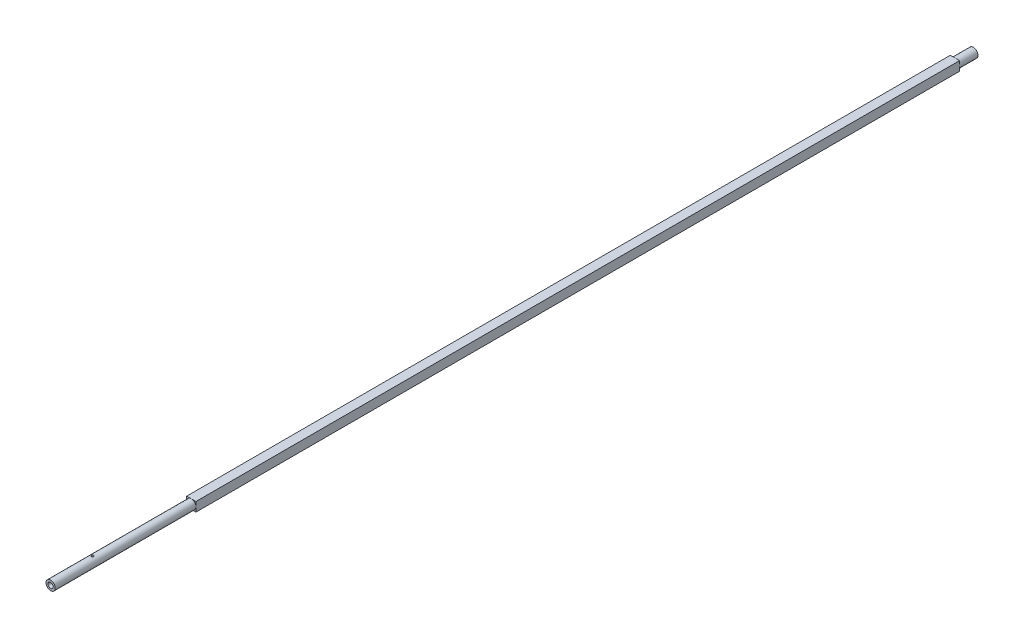
SolidWorks part; units mm, degrees
material "1060 Alloy"
ref_plane "Front Plane" through (0, 0, 0) normal (0, 0, 1) x (1, 0, 0)
ref_plane "Top Plane" through (0, 0, 0) normal (0, 1, 0) x (1, 0, 0)
ref_plane "Right Plane" through (0, 0, 0) normal (1, 0, 0) x (0, 0, -1)
sketch "Sketch1" plane through (0, 0, 0) normal (1, 0, 0) x (0, 0, -1)
  line L0 (0, 0) -> (-3.0596, 0) construction
  line L1 (533.7, 1.805) -> (528.7, 0)
  line L2 (-96.02, 1.805) -> (-96.02, 3.155)
  line L3 (-96.02, 3.155) -> (533.7, 3.155)
  line L4 (533.7, 1.805) -> (533.7, 3.155)
  line L5 (-96.02, 1.805) -> (-91.02, 0)
  line L6 (528.7, 0) -> (-91.02, 0)
  line L7 (0, 0) -> (0, 11.9284) construction
  line L8 (0, 0) -> (-91.02, 0) construction
  line L9 (624.72, 0) -> (533.7, 0) construction
  line L10 (533.7, 0) -> (533.7, 1.805) construction
  dimension "D1" = 6.31
  dimension "D2" = 5
  dimension "D3" = 3.61
  dimension "D4" = 533.7
  dimension "D5" = 96.02
  dimension "D6" = 5
revolve "Revolve1" add sketch "Sketch1" angle 360 about L0
sketch "Sketch5" plane through (0, 0, 0) normal (0, 1, 0) x (1, 0, 0)
  line L0 (3.155, 533.7) -> (-3.155, 533.7) construction
  line L1 (3.16, 521.14) -> (-3.16, 521.14)
  line L2 (3.16, 521.14) -> (3.16, 0)
  line L3 (3.16, 0) -> (-3.16, 0)
  line L4 (-3.16, 521.14) -> (-3.16, 0)
  line L5 (0, 0) -> (0, 540.4341) construction
  dimension "D1" = 12.56
  dimension "D2" = 6.32
extrude "Boss-Extrude2" add sketch "Sketch5" along normal blind 3.16 and the other way blind 3.16
sketch "Sketch4" plane through (0, 0, 0) normal (0, 1, 0) x (1, 0, 0)
  line L0 (0, -96.02) -> (0, -67.495) construction
  line L1 (0, -68.27) -> (4.3679, -68.27) construction
  line L2 (-3.155, -96.02) -> (3.155, -96.02) construction
  circle A0 centre (0, -67.495) radius 0.775
  dimension "D2" = 1.55
  dimension "D1" = 27.75
extrude "Cut-Extrude1" cut sketch "Sketch4" against normal through all and the other way through all
